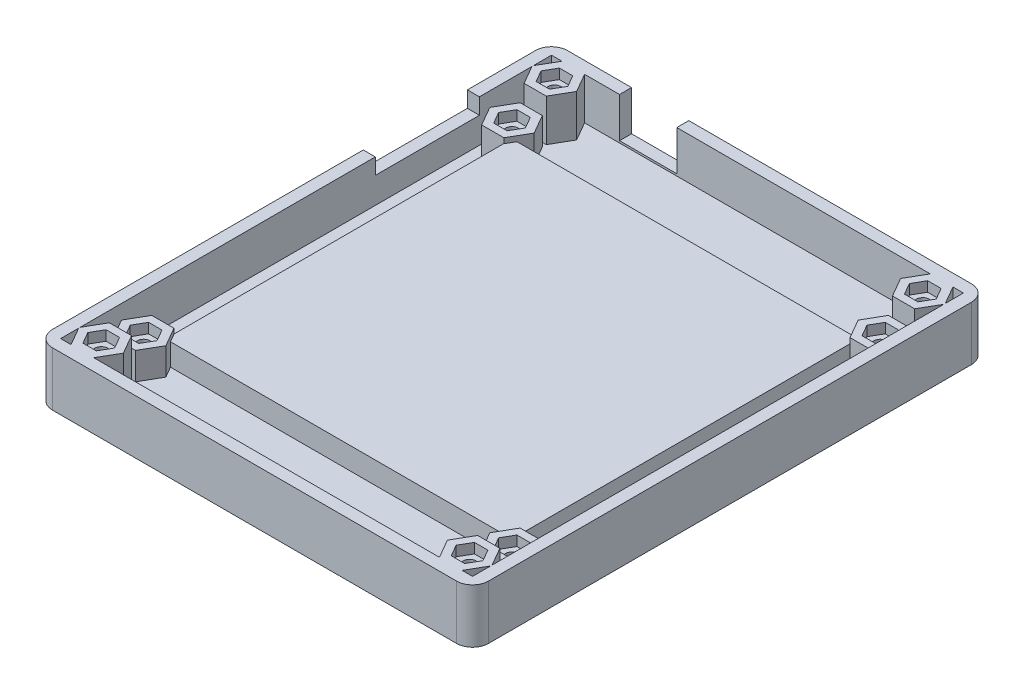
SolidWorks part; units mm, degrees
ref_plane "Přední rovina" through (0, 0, 0) normal (0, 0, 1) x (1, 0, 0)
ref_plane "Horní rovina" through (0, 0, 0) normal (0, 1, 0) x (1, 0, 0)
ref_plane "Pravá rovina" through (0, 0, 0) normal (1, 0, 0) x (0, 0, -1)
sketch "Skica1" plane through (0, 0, 0) normal (0, 1, 0) x (1, 0, 0)
  line L0 (0, 0) -> (-100, 100) construction
  line L1 (-50, 50) -> (50, 50) construction
  line L2 (-50, 50) -> (-50, -50) construction
  line L3 (-50, -50) -> (50, -50) construction
  line L4 (50, 50) -> (50, -50) construction
  line L5 (-50, 50) -> (50, -50) construction
  line L6 (-50, -50) -> (50, 50) construction
  line L7 (-47.6743, 43.1) -> (-44.3257, 43.1)
  line L8 (-44.3257, 43.1) -> (-42.6514, 46)
  line L9 (-42.6514, 46) -> (-44.3257, 48.9)
  line L10 (-44.3257, 48.9) -> (-47.6743, 48.9)
  line L11 (-47.6743, 48.9) -> (-49.3486, 46)
  line L12 (-49.3486, 46) -> (-47.6743, 43.1)
  line L13 (-48.7713, 41.2) -> (-43.2287, 41.2)
  line L14 (-43.2287, 41.2) -> (-40.4574, 46)
  line L15 (-40.4574, 46) -> (-43.2287, 50.8)
  line L16 (-43.2287, 50.8) -> (-48.7713, 50.8)
  line L17 (-48.7713, 50.8) -> (-51.5426, 46)
  line L18 (-51.5426, 46) -> (-48.7713, 41.2)
  line L19 (0, 81.3987) -> (0, -91.9033) construction
  line L20 (-42.6514, 56.6) -> (-44.3257, 59.5)
  line L21 (-44.3257, 59.5) -> (-47.6743, 59.5)
  line L22 (-47.6743, 59.5) -> (-49.3486, 56.6)
  line L23 (-49.3486, 56.6) -> (-47.6743, 53.7)
  line L24 (-47.6743, 53.7) -> (-44.3257, 53.7)
  line L25 (-44.3257, 53.7) -> (-42.6514, 56.6)
  line L26 (-48.7713, 51.8) -> (-43.2287, 51.8)
  line L27 (-43.2287, 51.8) -> (-40.4574, 56.6)
  line L28 (-40.4574, 56.6) -> (-43.2287, 61.4)
  line L29 (-43.2287, 61.4) -> (-48.7713, 61.4)
  line L30 (-48.7713, 61.4) -> (-51.5426, 56.6)
  line L31 (-51.5426, 56.6) -> (-48.7713, 51.8)
  line L36 (74.9355, -74.9355) -> (-74.9355, 74.9355) construction
  line L37 (74.9355, 74.9355) -> (-74.9355, -74.9355) construction
  line L38 (-54.4426, -64.3) -> (54.4426, -64.3)
  line L39 (-54.4426, -64.3) -> (-54.4426, 64.3)
  line L40 (-54.4426, 64.3) -> (54.4426, 64.3)
  line L41 (54.4426, -64.3) -> (54.4426, 64.3)
  line L42 (-54.4426, -64.3) -> (54.4426, 64.3) construction
  line L43 (-54.4426, 64.3) -> (54.4426, -64.3) construction
  line L44 (-106.951, 0) -> (125.2961, 0) construction
  line L45 (-46, 37.8836) -> (-46, 68.4593) construction
  line L47 (-51.4426, -61.3) -> (51.4426, -61.3)
  line L48 (-51.4426, -61.3) -> (-51.4426, 61.3)
  line L49 (-51.4426, 61.3) -> (51.4426, 61.3)
  line L50 (51.4426, -61.3) -> (51.4426, 61.3)
  line L51 (-51.4426, -61.3) -> (51.4426, 61.3) construction
  line L52 (-51.4426, 61.3) -> (51.4426, -61.3) construction
  circle A0 centre (-46, 46) radius 2.9 construction
  circle A1 centre (-46, 46) radius 4.8 construction
  circle A2 centre (-46, 56.6) radius 2.9 construction
  circle A3 centre (-46, 56.6) radius 4.8 construction
  circle A4 centre (-46, 46) radius 1.6
  circle A5 centre (-46, 56.6) radius 1.6
  point P0 (0, 0)
  point P7 (-41.8431, 43.6)
  dimension "D9" = 3
  dimension "D10" = 3
  dimension "D11" = 0.1
  dimension "D12" = 0.1
  dimension "D13" = 3.2
  dimension "D14" = 3.2
  dimension "D1" = 100
  dimension "D2" = 100
  dimension "D3" = 5.8
  dimension "D4" = 4
  dimension "D5" = 9.6
  dimension "D6" = 5.8
  dimension "D7" = 9.6
  dimension "D8" = 1
extrude "Přidat vysunutím25" add sketch "Skica1" against normal blind 3 contours L49 L48 L30 | L20 L21 L22 L23 L24 L25 | L7 L8 L9 L10 L11 L12 | L48 L47 L50 L49 | L13 L14 L15 L16 L17 L18 | L26 L27 L28 L29 L30 L31 region at (-50.5714, 0, -59.7911)
extrude "Přidat vysunutím26" add sketch "Skica1<21>" against normal blind 3 and the other way blind 10.5 contours L38 L41 L40 L39 L50 L47 L48 L18 L17 L31 L30 L49 L29 L28 | L18 L48 L17 | L31 L48 L30 | L30 L49 L28 L29 region at (-51.4759, 0, -46) region at (-51.4759, 0, -56.6) region at (-46, 0, -61.3498) region at (-52.7575, 0, 0)
sketch "Skica1<21>" plane through (0, 0, 0) normal (0, 1, 0) x (1, 0, 0) same geometry as "Skica1"
extrude "Přidat vysunutím28" add sketch "Skica1<23>" along normal blind 6.8 contours L48 L18 L13 L14 L15 L16 L17 L12 L11 L10 L9 L8 L7 | L18 L48 L17 region at (-49.9806, 0, -43.5863) region at (-51.4759, 0, -46)
sketch "Skica1<23>" plane through (0, 0, 0) normal (0, 1, 0) x (1, 0, 0) same geometry as "Skica1"
extrude "Přidat vysunutím29" add sketch "Skica1<24>" along normal blind 4.3 contours L11 L12 L7 L8 L9 L10 region at (-48.4347, 0, -44.5943)
sketch "Skica1<24>" plane through (0, 0, 0) normal (0, 1, 0) x (1, 0, 0) same geometry as "Skica1"
pattern_linear "LinPole3" count 2 spacing 92 along (1, 0, 0) count 2 spacing 92 along (0, 0, 1) of "Přidat vysunutím28", "Přidat vysunutím29"
extrude "Přidat vysunutím30" add sketch "Skica1<25>" along normal blind 10.5 contours L49 L30 L48 L31 L26 L27 L28 L25 L24 L23 L22 L21 L20 | L30 L49 L28 L29 | L31 L48 L30 region at (-51.2973, 0, -56.6) region at (-51.4759, 0, -56.6) region at (-46, 0, -61.3498)
sketch "Skica1<25>" plane through (0, 0, 0) normal (0, 1, 0) x (1, 0, 0) same geometry as "Skica1"
extrude "Přidat vysunutím31" add sketch "Skica1<26>" along normal blind 8 contours L24 L25 L20 L21 L22 L23 A5 region at (-43.5653, 0, -55.1943)
sketch "Skica1<26>" plane through (0, 0, 0) normal (0, 1, 0) x (1, 0, 0) same geometry as "Skica1"
pattern_linear "LinPole4" count 2 spacing 92 along (1, 0, 0) count 2 spacing 113.2 along (0, 0, 1) of "Přidat vysunutím31", "Přidat vysunutím30"
sketch "Skica8" plane through (0, 0, 0) normal (0, 1, 0) x (1, 0, 0)
  line L1 (-43.2691, -43.2691) -> (43.2691, -43.2691)
  line L2 (-43.2691, -43.2691) -> (-43.2691, 43.2691)
  line L3 (-43.2691, 43.2691) -> (43.2691, 43.2691)
  line L4 (43.2691, -43.2691) -> (43.2691, 43.2691)
  line L5 (-43.2691, -43.2691) -> (43.2691, 43.2691) construction
  line L6 (-43.2691, 43.2691) -> (43.2691, -43.2691) construction
  point P0 (0, 0)
  dimension "D1" = 86.5383
extrude "Přidat vysunutím32" add sketch "Skica8" along normal blind 5.5
fillet "Zaoblit4" radius 4 4 edges at (-54.4426, 3.75, 64.3) (54.4426, 3.75, 64.3) (54.4426, 3.75, -64.3) (-54.4426, 3.75, -64.3)
sketch "Skica9" plane through (-54.4426, 0, 0) normal (-1, 0, 0) x (0, 0, 1)
  line L0 (60.3, 10.5) -> (-60.3, 10.5) construction
  line L1 (-17.3, 6.5) -> (-43.3, 6.5)
  line L2 (-17.3, 6.5) -> (-17.3, 10.5)
  line L3 (-17.3, 10.5) -> (-43.3, 10.5)
  line L4 (-43.3, 6.5) -> (-43.3, 10.5)
  line L5 (-17.3, 6.5) -> (-43.3, 10.5) construction
  line L6 (-17.3, 10.5) -> (-43.3, 6.5) construction
  line L7 (-64.3, -3) -> (-64.3, 10.5) construction
  point P0 (-30.3, 8.5)
  dimension "D1" = 26
  dimension "D2" = 21
  dimension "D3" = 4
extrude "Odebrat vysunutím1" cut sketch "Skica9" against normal blind 4 contours L4 L3 L2 L1
sketch "Skica10" plane through (0, 0, -64.3) normal (0, 0, -1) x (-1, 0, 0)
  line L0 (50.4426, 10.5) -> (-50.4426, 10.5) construction
  line L1 (20.1426, 0.5) -> (34.4426, 0.5)
  line L2 (20.1426, 0.5) -> (20.1426, 10.5)
  line L3 (20.1426, 10.5) -> (34.4426, 10.5)
  line L4 (34.4426, 0.5) -> (34.4426, 10.5)
  line L5 (54.4426, 10.5) -> (54.4426, -3) construction
  dimension "D1" = 10
  dimension "D2" = 14.3
  dimension "D3" = 20
extrude "Odebrat vysunutím2" cut sketch "Skica10" against normal blind 5
